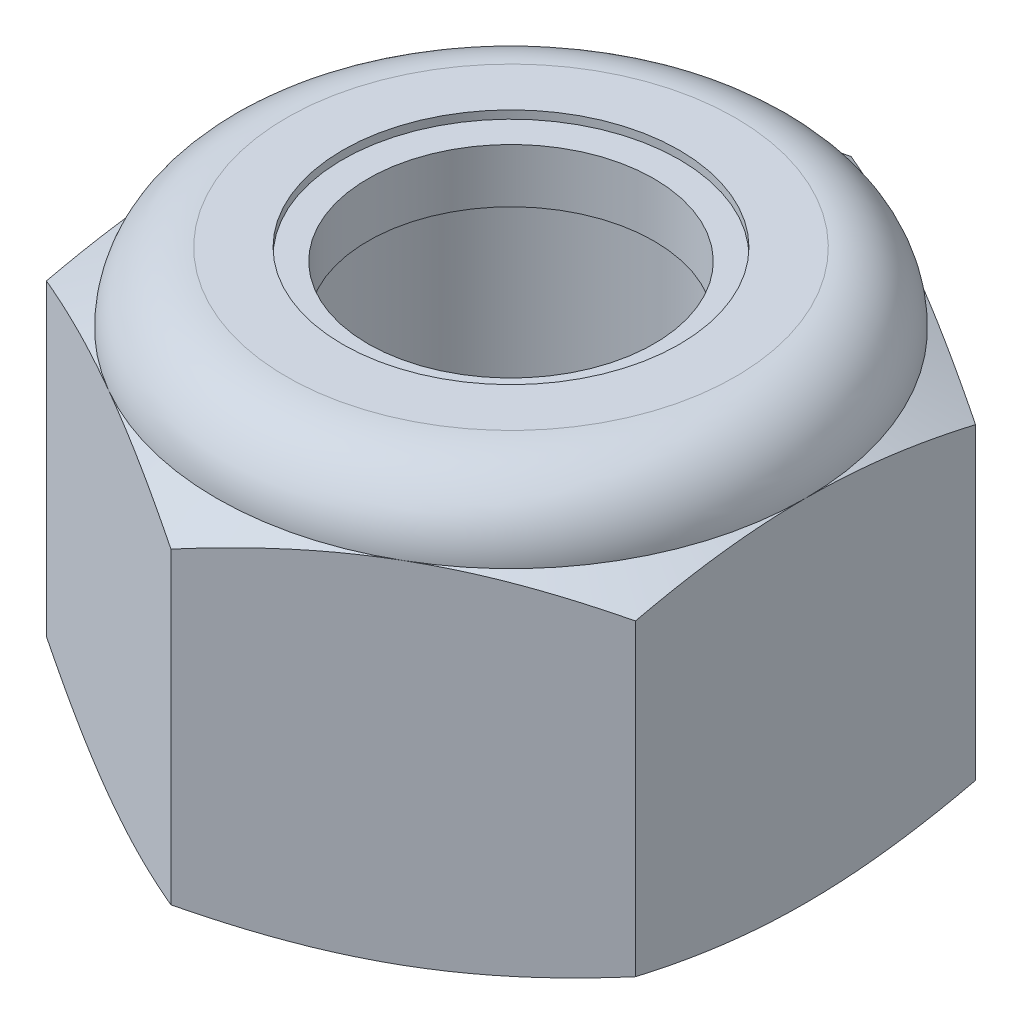
SolidWorks part; units mm, degrees
ref_plane "Front" through (0, 0, 0) normal (0, 0, 1) x (1, 0, 0)
ref_plane "Top" through (0, 0, 0) normal (0, 1, 0) x (1, 0, 0)
ref_plane "Right" through (0, 0, 0) normal (1, 0, 0) x (0, 0, -1)
sketch "Sketch1" plane through (0, 0, 0) normal (1, 0, 0) x (0, 0, -1)
  line L0 (0, 0) -> (0, 7.9375) construction
  line L1 (5.5562, 0) -> (-5.5562, 0) construction
  line L2 (-3.175, 7.9375) -> (3.175, 7.9375) construction
  line L3 (3.175, 7.9375) -> (3.175, 6.6675) construction
  point P9 (-3.175, 7.9375)
  point P10 (3.175, 7.9375)
  point P11 (5.5562, 0)
  dimension "Height" = 7.9375
  dimension "Hex Flats" = 11.1125
  dimension "Thread Dia" = 6.35
  dimension "Thread Pitch" = 1.27
sketch "Sketch13" plane through (0, 0, 0) normal (0, 1, 0) x (1, 0, 0)
  line L1 (0, 6.4158) -> (-5.5563, 3.2079)
  line L2 (-5.5563, 3.2079) -> (-5.5562, -3.2079)
  line L3 (-5.5562, -3.2079) -> (0, -6.4158)
  line L4 (0, -6.4158) -> (5.5563, -3.2079)
  line L5 (5.5563, -3.2079) -> (5.5563, 3.2079)
  line L6 (5.5563, 3.2079) -> (0, 6.4158)
  circle A0 centre (0, 0) radius 5.5562 construction
  circle A1 centre (0, 0) radius 3.175
  point P11 (0, -3.175)
  point P13 (0, 3.175)
extrude "Extrude1" add sketch "Sketch13" along normal up to vertex (7.9375 mm away) up to point (0, 7.9375, 0)
sketch "Sketch5" plane through (0, 0, 0) normal (1, 0, 0) x (0, 0, -1)
  line L0 (0, 0) -> (5.5562, 0)
  line L1 (5.5562, 0) -> (6.4158, 0.4008)
  line L2 (6.4158, 0.4008) -> (6.4158, 6.2138)
  line L3 (6.4158, 6.2138) -> (5.5562, 6.6146)
  line L4 (4.2333, 7.9375) -> (4.2333, 9.2075)
  line L5 (4.2333, 9.2075) -> (7.6858, 9.2075)
  line L6 (7.6858, 9.2075) -> (7.6858, -1.27)
  line L7 (7.6858, -1.27) -> (0, -1.27)
  line L8 (0, -1.27) -> (0, 0)
  line L9 (5.5562, 6.6146) -> (5.5562, 0) construction
  line L12 (6.4158, 7.9375) -> (6.4158, 0) construction
  line L13 (6.4158, 3.9688) -> (7.6858, 3.9688) construction
  line L15 (0, 0) -> (0, 9.2075) construction
  line L18 (5.5562, 0) -> (-5.5562, 0) construction
  line L19 (3.2079, 7.9375) -> (6.4158, 7.9375) construction
  line L20 (0, 9.2075) -> (4.2333, 9.2075) construction
  line L21 (3.2079, 0) -> (6.4158, 0) construction
  arc A0 (5.5562, 6.6146) -> (4.2333, 7.9375) centre (4.2333, 6.6146) ccw
  dimension "D1" = 25
  dimension "D2" = 1.27
  dimension "D4" = 1.3229
revolve "Cut-Revolve3" cut sketch "Sketch5" angle 360 about L15
sketch "Sketch4" plane through (0, 0, 0) normal (1, 0, 0) x (0, 0, -1)
  line L0 (0, 6.6146) -> (3.4925, 6.6146)
  line L1 (3.4925, 6.6146) -> (0, 4.986)
  line L3 (0, 1.6286) -> (3.4925, 0)
  line L4 (3.4925, 0) -> (0, 0)
  line L5 (0, 0) -> (0, 6.6146) construction
  line L10 (0, 0) -> (0, 7.9375) construction
  line L11 (0, 1.6286) -> (0, 0)
  line L12 (0, 6.6146) -> (0, 4.986)
  line L13 (4.8119, 6.6146) -> (0, 6.6146) construction
  dimension "D1" = 25
  dimension "D2" = 6.985
sketch "Sketch6" plane through (0, 0, 0) normal (1, 0, 0) x (0, 0, -1)
  line L0 (0, 6.6146) -> (5.4039, 6.6146)
  line L1 (4.2333, 7.7851) -> (2.1167, 7.7851)
  line L2 (0, 9.2075) -> (0, 6.6146)
  line L3 (2.1167, 9.2075) -> (0, 9.2075)
  line L4 (0, 9.2075) -> (4.2333, 9.2075) construction
  line L5 (0, 0) -> (0, 9.2075) construction
  line L6 (0, 9.2075) -> (0, 0) construction
  line L7 (2.1167, 7.7851) -> (2.1167, 9.2075)
  line L8 (4.2333, 7.9375) -> (4.2333, 7.7851) construction
  line L9 (2.1167, 7.7851) -> (0, 7.7851) construction
  line L10 (0, 7.7851) -> (0, 4.986) construction
  arc A0 (5.4039, 6.6146) -> (4.2333, 7.7851) centre (4.2333, 6.6146) ccw
  arc A1 (5.5562, 6.6146) -> (4.2333, 7.9375) centre (4.2333, 6.6146) ccw construction
  dimension "D1" = 0.1524
revolve "Cut-Revolve4" cut sketch "Sketch6" angle 360 about L6
revolve "Cut-Revolve2" cut sketch "Sketch4" angle 360 about L5
sketch "Sketch7" plane through (0, 0, 0) normal (1, 0, 0) x (0, 0, -1)
  line L0 (2.6988, 6.6908) -> (5.325, 6.6908)
  line L1 (4.2333, 7.7089) -> (2.6988, 7.7089)
  line L2 (2.6988, 7.7089) -> (2.6988, 6.6908)
  line L3 (2.6988, 6.6908) -> (0, 6.6908) construction
  line L4 (0, 6.6908) -> (0, 7.7089) construction
  line L5 (0, 7.7089) -> (2.6988, 7.7089) construction
  line L6 (2.6988, 6.6908) -> (2.6988, 6.6146) construction
  line L7 (0, 6.6146) -> (5.4039, 6.6146) construction
  line L8 (4.2333, 7.7089) -> (4.2333, 7.7851) construction
  arc A0 (5.325, 6.6908) -> (4.2333, 7.7089) centre (4.2333, 6.6146) ccw
  arc A2 (5.4039, 6.6146) -> (4.2333, 7.7851) centre (4.2333, 6.6146) ccw construction
  point P15 (2.6988, 7.7089)
  point P18 (-3.466, 7.7089)
  point P19 (3.466, 7.7089)
  dimension "D1" = 0.0762
  dimension "D2" = 5.3975
revolve "Revolve2" add sketch "Sketch7" angle 360 about L4
sketch "Sketch2" [suppressed] plane through (0, 0, 0) normal (1, 0, 0) x (0, 0, -1)
  line L0 (-3.175, 0) -> (-3.175, 6.6146) construction
  line L1 (0, 0) -> (3.175, 0)
  line L2 (0, 0) -> (0, 6.6146)
  line L3 (0, 6.6146) -> (3.175, 6.6146)
  line L4 (3.175, 0) -> (3.175, 6.6146)
  line L6 (4.8119, 6.6146) -> (5.5562, 6.6146) construction
  line L7 (0, -3.175) -> (0, 0) construction
revolve "Revolve1" [suppressed] add sketch "Sketch2" angle 360 about L7
sketch "Sketch9" [suppressed] plane through (0, 0, 0) normal (1, 0, 0) x (0, 0, -1)
  line L0 (3.3125, 7.8052) -> (3.3125, 6.5352) construction
  line L1 (3.3125, 6.5352) -> (2.2126, 7.1702) construction
  line L2 (2.2126, 7.1702) -> (3.3125, 7.8052) construction
  line L3 (2.3501, 7.2496) -> (2.3501, 7.0908) construction
  line L4 (3.175, 7.7258) -> (3.175, 6.6146) construction
  line L5 (2.2126, 7.1702) -> (2.3501, 7.1702) construction
  line L6 (3.175, 7.1702) -> (3.3125, 7.1702) construction
  line L7 (3.2437, 7.1702) -> (3.2437, 7.7655) construction
  line L8 (3.3125, 6.5352) -> (3.2437, 7.7655)
  line L9 (3.2437, 7.7655) -> (2.3501, 7.2496)
  line L10 (2.3501, 7.2496) -> (2.3501, 7.0908)
  line L11 (2.3501, 7.0908) -> (3.3125, 6.5352)
  dimension "D1" = 1.27
  dimension "D2" = 0.1588
sketch "Sketch10" [suppressed] plane through (0, 6.6146, 0) normal (0, 1, 0) x (1, 0, 0)
  circle A1 centre (0, 0) radius 3.175
  circle A2 centre (0, 0) radius 3.175
  dimension "D1" = 0
curve "Helix/Spiral1" [suppressed] pitch 1.27 height 9.2075 turns 7.25
sweep "Cut-Sweep1" [suppressed] cut profiles "Sketch9" path "Helix/Spiral1"
sketch "Sketch11" [suppressed] plane through (0, 0, 0) normal (1, 0, 0) x (0, 0, -1)
  line L0 (0, 0) -> (0, 7.9375) construction
  line L1 (5.5562, 0) -> (-5.5562, 0) construction
  line L4 (0, 7.9375) -> (0, 0) construction
  line L5 (0, 3.9688) -> (3.175, 3.9688) construction
  line L6 (0, 0) -> (3.4925, 0)
  line L7 (0, 1.6286) -> (0, 0)
  line L8 (3.4925, 0) -> (0, 1.6286)
  dimension "D1" = 6.985
  dimension "D2" = 25
revolve "Revolve3" [suppressed] add sketch "Sketch11" angle 360 about L4
sketch "Sketch12" [suppressed] plane through (0, 0, 0) normal (1, 0, 0) x (0, 0, -1)
  line L0 (3.4925, 6.6146) -> (0, 6.6146)
  line L1 (0, 6.6146) -> (0, 0)
  line L2 (0, 0) -> (3.4925, 0)
  line L3 (5.5562, 0) -> (-5.5562, 0) construction
  line L4 (3.4925, 0) -> (3.4925, 6.6146)
  line L5 (-3.4925, 0) -> (3.4925, 0) construction
revolve "Revolve4" [suppressed] add sketch "Sketch12" angle 360 about L0
combine bodies "Combine1" [suppressed] operation type add bodies to combine 136 133
equation "\"D4@Sketch5\" = \"Height@Sketch1\" / 6"
equation "\"D1@Sketch9\" = \"Thread Pitch@Sketch1\""
equation "\"D2@Sketch9\" = \"Thread Pitch@Sketch1\" / 8"
equation "\"D4@Helix/Spiral1\" = \"Thread Pitch@Sketch1\""
equation "\"D3@Helix/Spiral1\" = \"Thread Pitch@Sketch1\" + \"Height@Sketch1\""
equation "\"D2@Sketch4\" = \"Thread Dia@Sketch1\" * 1.1"
equation "\"D1@Sketch11\" = \"Thread Dia@Sketch1\" * 1.1"
equation "\"D2@Sketch7\" = \"Thread Dia@Sketch1\" * .85"
